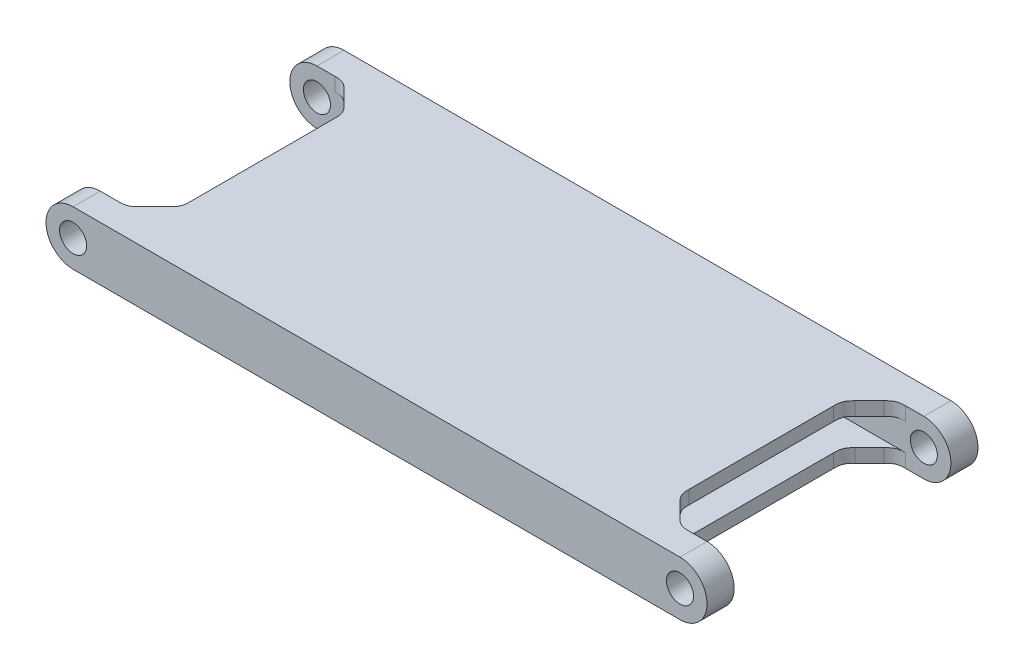
SolidWorks part; units mm, degrees
ref_plane "Front Plane" through (0, 0, 0) normal (0, 0, 1) x (1, 0, 0)
ref_plane "Top Plane" through (0, 0, 0) normal (0, 1, 0) x (1, 0, 0)
ref_plane "Right Plane" through (0, 0, 0) normal (1, 0, 0) x (0, 0, -1)
sketch "Sketch1" plane through (0, 0, 0) normal (0, 0, 1) x (1, 0, 0)
  line L0 (-112, 0) -> (112, 0) construction
  line L1 (-112, 10) -> (112, 10)
  line L2 (-112, -10) -> (112, -10)
  line L3 (0, -5.5) -> (0, 5.5) construction
  arc A0 (-112, 10) -> (-112, -10) centre (-112, 0) ccw
  arc A1 (112, -10) -> (112, 10) centre (112, 0) ccw
  circle A2 centre (-112, 0) radius 5
  circle A3 centre (112, 0) radius 5
  point P2 (0, 0)
  dimension "D2" = 10
  dimension "D3" = 5
  dimension "D1" = 224
extrude "Boss-Extrude1" add sketch "Sketch1" along normal mid plane 10
sketch "Sketch2" plane through (0, 0, 5) normal (0, 0, 1) x (1, 0, 0)
  line L8 (-112, -5) -> (112, -5)
  line L9 (112, 5) -> (-112, 5)
  line L10 (-112, -5) -> (112, -5)
  line L11 (112, 5) -> (-112, 5)
  line L12 (-112, -10) -> (112, -10)
  line L13 (112, 10) -> (-112, 10)
  line L14 (-112, -10) -> (112, -10)
  line L15 (112, 10) -> (-112, 10)
  arc A4 (-112, 5) -> (-112, -5) centre (-112, 0) ccw
  arc A5 (112, -5) -> (112, 5) centre (112, 0) ccw
  arc A6 (-112, 5) -> (-112, -5) centre (-112, 0) ccw
  arc A7 (112, -5) -> (112, 5) centre (112, 0) ccw
  arc A8 (-112, 10) -> (-112, -10) centre (-112, 0) ccw
  arc A9 (112, -10) -> (112, 10) centre (112, 0) ccw
  arc A10 (-112, 10) -> (-112, -10) centre (-112, 0) ccw
  arc A11 (112, -10) -> (112, 10) centre (112, 0) ccw
  dimension "D1" = 5
  dimension "D2" = 0
extrude "Boss-Extrude2" add sketch "Sketch2" along normal blind 40
mirror "Mirror1" about plane through (-112, 0, 45) normal (0, 0, 1) of bodies 103
sketch "Sketch4" plane through (0, 10, 0) normal (0, 1, 0) x (1, 0, 0)
  line L0 (112, -95) -> (-112, -95) construction
  line L1 (-140.2233, -5) -> (-92, -5)
  line L2 (-140.2233, -5) -> (-140.2233, -85)
  line L3 (-140.2233, -85) -> (-92, -85)
  line L4 (-92, -5) -> (-92, -85)
  line L5 (112, 5) -> (-112, 5) construction
  line L6 (-112, -95) -> (-112, 5) construction
  line L7 (0, -11) -> (0, 11) construction
  line L8 (140.2233, -85) -> (92, -85)
  line L9 (92, -5) -> (92, -85)
  line L10 (140.2233, -5) -> (92, -5)
  line L11 (140.2233, -5) -> (140.2233, -85)
  dimension "D1" = 10
  dimension "D2" = 10
  dimension "D3" = 20
extrude "Cut-Extrude1" cut sketch "Sketch4" against normal blind 40
chamfer "Chamfer1" distance 10 angle 45 8 edges at (-92, -7.5, 5) (-92, 7.5, 5) (-92, -7.5, 85) (-92, 7.5, 85) (92, 7.5, 85) (92, -7.5, 85) (92, 7.5, 5) (92, -7.5, 5)
fillet "Fillet1" radius 8 16 edges at (-92, -7.5, 15) (-102, -7.5, 5) (92, -7.5, 15) (92, -7.5, 75) (102, -7.5, 85) (-102, -7.5, 85) (-92, -7.5, 75) (102, -7.5, 5) (-92, 7.5, 75) (-102, 7.5, 85) (102, 7.5, 85) (92, 7.5, 75) (92, 7.5, 15) (-102, 7.5, 5) (-92, 7.5, 15) (102, 7.5, 5) curvature continuous yes
